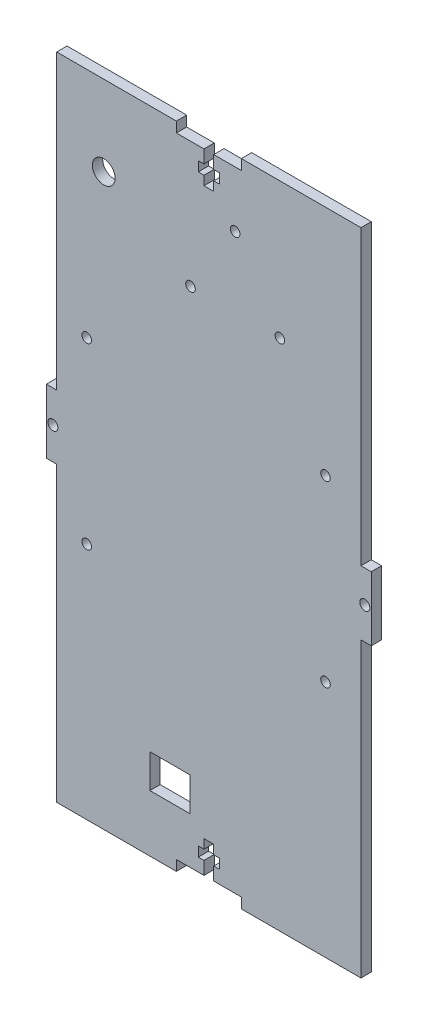
SolidWorks part; units mm, degrees
ref_plane "Front Plane" through (0, 0, 0) normal (0, 0, 1) x (1, 0, 0)
ref_plane "Top Plane" through (0, 0, 0) normal (0, 1, 0) x (1, 0, 0)
ref_plane "Right Plane" through (0, 0, 0) normal (1, 0, 0) x (0, 0, -1)
sketch "Sketch1" plane through (0, 0, 0) normal (0, 0, 1) x (1, 0, 0)
  line L0 (0, 40) -> (0, -40) construction
  line L5 (-50, -100) -> (50, 100) construction
  line L6 (-50, 100) -> (50, -100) construction
  line L7 (-100, 0) -> (100, 0) construction
  line L32 (-50, 100) -> (50, 100)
  line L35 (50, 100) -> (50, -100)
  line L36 (50, -100) -> (-50, -100)
  line L37 (-50, -100) -> (-50, 100)
  point P0 (0, 0)
  dimension "D1" = 100
  dimension "D2" = 200
extrude "Boss-Extrude2" add sketch "Sketch1" along normal blind 3.18
sketch "Sketch2" plane through (0, 0, 3.18) normal (0, 0, 1) x (1, 0, 0)
  line L0 (0, -100) -> (0, 100) construction
  line L1 (-123.0225, 0) -> (147.0753, 0) construction
  line L2 (50, 100) -> (-50, 100) construction
  line L4 (-10, 100) -> (-10, 96.82)
  line L5 (-10, 96.82) -> (-1.5, 96.82)
  line L6 (10, 100) -> (10, 96.82)
  line L7 (1.5, 96.82) -> (10, 96.82)
  line L9 (-1.5, 96.82) -> (-1.5, 92.82)
  line L10 (-1.5, 87) -> (1.5, 87)
  line L11 (1.5, 96.82) -> (1.5, 92.82)
  line L12 (-3.25, 92.82) -> (-1.5, 92.82)
  line L13 (-3.25, 92.82) -> (-3.25, 89.82)
  line L14 (-3.25, 89.82) -> (-1.5, 89.82)
  line L15 (3.25, 92.82) -> (3.25, 89.82)
  line L16 (1.5, 92.82) -> (3.25, 92.82)
  line L17 (-1.5, 89.82) -> (-1.5, 87)
  line L18 (1.5, 89.82) -> (1.5, 87)
  line L19 (1.5, 89.82) -> (3.25, 89.82)
  line L20 (-10, 100) -> (10, 100)
  line L21 (-50, -100) -> (50, -100) construction
  line L22 (-50, 100) -> (-50, -100) construction
  line L23 (-50, 9.875) -> (-46.82, 9.875)
  line L24 (-50, 9.875) -> (-50, 100)
  line L25 (-50, 100) -> (-46.82, 100)
  line L26 (-46.82, 9.875) -> (-46.82, 100)
  line L28 (-50, -9.875) -> (-46.82, -9.875)
  line L29 (-50, -9.875) -> (-50, -100)
  line L30 (-50, -100) -> (-46.82, -100)
  line L31 (-46.82, -9.875) -> (-46.82, -100)
  circle A0 centre (-48, 0) radius 1.55
  dimension "D11" = 3.1
  dimension "D12" = 2
  dimension "D1" = 4
  dimension "D2" = 3
  dimension "D3" = 3
  dimension "D4" = 20
  dimension "D5" = 6.5
  dimension "D6" = 3.18
  dimension "D7" = 13
  dimension "D8" = 19.75
  dimension "D9" = 3.18
  dimension "D10" = 3.18
extrude "Cut-Extrude1" cut sketch "Sketch2" against normal through all
mirror "Mirror1" about plane through (0, 0, 0) normal (0, 1, 0) of "Cut-Extrude1"
mirror "Mirror3" about plane through (0, 0, 0) normal (1, 0, 0) of "Cut-Extrude1"
sketch "Sketch4" plane through (0, 0, 3.18) normal (0, 0, 1) x (1, 0, 0)
  line L5 (-18.15, -82.52) -> (-5.7964, -82.52)
  line L6 (-18.15, -82.52) -> (-18.15, -72.1664)
  line L7 (-18.15, -72.1664) -> (-5.7964, -72.1664)
  line L8 (-5.7964, -82.52) -> (-5.7964, -72.1664)
  arc A0 (-5.65, -72.52) -> (-6.15, -72.02) centre (-6.15, -72.52) ccw construction
extrude "Cut-Extrude3" cut sketch "Sketch4" against normal through all
sketch "Sketch5" plane through (0, 0, 3.18) normal (0, 0, 1) x (1, 0, 0)
  circle A0 centre (-37.5809, 28.4641) radius 1.47
  circle A1 centre (35.9045, 28.4641) radius 1.47
  circle A2 centre (-37.5809, -26.5359) radius 1.47
  circle A3 centre (35.9045, -26.5359) radius 1.47
  circle A4 centre (-37.5809, 28.4641) radius 1.47 construction
  circle A5 centre (35.9045, 28.4641) radius 1.47 construction
  circle A6 centre (35.9045, -26.5359) radius 1.47 construction
  circle A8 centre (-37.5809, -26.5359) radius 1.47 construction
extrude "Cut-Extrude4" cut sketch "Sketch5" against normal through all
sketch "Sketch6" plane through (0, 0, 3.18) normal (0, 0, 1) x (1, 0, 0)
  circle A0 centre (-5.6383, 58.12) radius 1.47
  circle A1 centre (8.1117, 79.62) radius 1.47
  circle A2 centre (21.8617, 58.12) radius 1.47
  circle A3 centre (-5.6383, 58.12) radius 1.4 construction
  circle A4 centre (8.1117, 79.62) radius 1.4 construction
  circle A5 centre (21.8617, 58.12) radius 1.4 construction
  dimension "D1" = 2.94
extrude "Cut-Extrude5" cut sketch "Sketch6" against normal through all
sketch "Sketch7" plane through (0, 0, 13.055) normal (0, 0, 1) x (1, 0, 0)
  circle A0 centre (-32.3543, 75.3033) radius 3.5
  circle A1 centre (-32.3543, 75.3033) radius 3.43 construction
  dimension "D1" = 7
extrude "Cut-Extrude6" cut sketch "Sketch7" against normal through all
